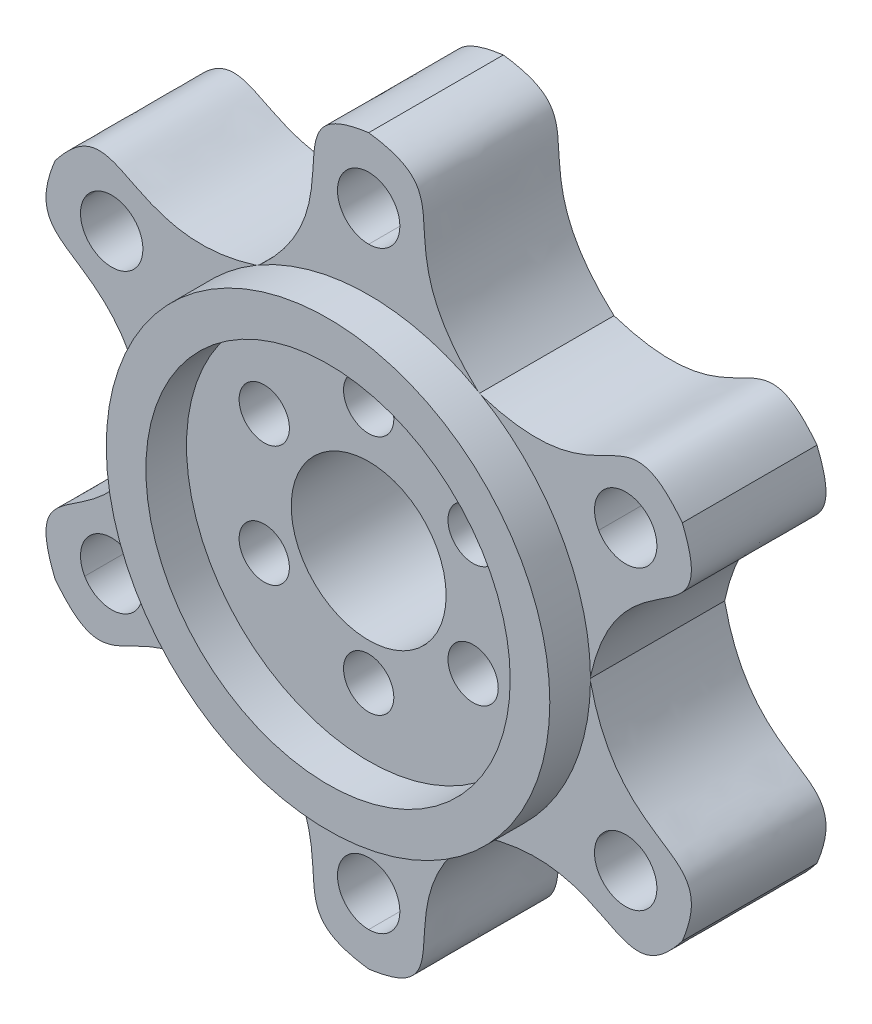
SolidWorks part; units mm, degrees
ref_plane "Front Plane" through (0, 0, 0) normal (0, 0, 1) x (1, 0, 0)
ref_plane "Top Plane" through (0, 0, 0) normal (0, 1, 0) x (1, 0, 0)
ref_plane "Right Plane" through (0, 0, 0) normal (1, 0, 0) x (0, 0, -1)
sketch "Sketch1" plane through (0, 0, 0) normal (0, 0, 1) x (1, 0, 0)
  line L0 (0, -55) -> (0, 55) construction
  line L1 (0, 0) -> (0, 45.72) construction
  circle A0 centre (0, 0) radius 9.779
  circle A1 centre (0, 0) radius 45.72
  circle A2 centre (0, 16.002) radius 3.175
  circle A3 centre (13.1849, 8.3897) radius 3.175
  circle A4 centre (13.1849, -6.8349) radius 3.175
  circle A5 centre (0, -14.4471) radius 3.175
  circle A6 centre (-13.1849, -6.8349) radius 3.175
  circle A7 centre (-13.1849, 8.3897) radius 3.175
  circle A8 centre (0, 37.465) radius 3.937
  circle A10 centre (32.4456, 18.7325) radius 3.937
  circle A11 centre (32.4456, -18.7325) radius 3.937
  circle A12 centre (0, -37.465) radius 3.937
  circle A13 centre (-32.4456, -18.7325) radius 3.937
  circle A14 centre (-32.4456, 18.7325) radius 3.937
  point P21 (0, 0.7774)
  point P36 (0, 0)
  dimension "D1" = 19.558
  dimension "D2" = 91.44
  dimension "D3" = 6.35
  dimension "D6" = 7.874
  dimension "D4" = 16.002
  dimension "D8" = 37.465
  dimension "D5" = 6
  dimension "D7" = 6
extrude "Boss-Extrude3" add sketch "Sketch1" along normal blind 17
sketch "Sketch2" plane through (0, 0, 17) normal (0, 0, 1) x (1, 0, 0)
  line L0 (0, -9.35) -> (0, 9.35) construction
  line L1 (-32.4456, 18.7325) -> (0, 37.465) construction
  line L2 (-16.2228, 28.0988) -> (-4.8895, 8.4689) construction
  line L3 (16.1678, 28.1305) -> (4.8344, 8.5004) construction
  line L6 (32.4456, -18.7325) -> (32.4456, 18.7325) construction
  line L7 (32.4456, 18.7325) -> (0, 37.465) construction
  line L8 (9.35, 0) -> (-9.35, 0) construction
  circle A0 centre (0, 0) radius 27.94 construction
  circle A1 centre (0, 0) radius 45.72 construction
  circle A2 centre (0, 0) radius 9.779 construction
  circle A3 centre (0, 0) radius 45.72
  spline S0 degree 3 poles (-13.97, 24.1967) (-0.9195, 35.9832) (-13.1193, 43.9586) (0, 45.72) knots 0 0 0 0 1 1 1 1
  spline S1 degree 3 poles (13.97, 24.1967) (0.9195, 35.9832) (13.1193, 43.9586) (0, 45.72) knots 0 0 0 0 1 1 1 1
  spline S2 degree 3 poles (-27.94, 0) (-31.6221, 17.1953) (-44.6289, 10.6177) (-39.5947, 22.86) knots 0 0 0 0 1 1 1 1
  spline S3 degree 3 poles (-13.97, 24.1967) (-30.7026, 18.7879) (-31.5096, 33.3409) (-39.5947, 22.86) knots 0 0 0 0 1 1 1 1
  spline S4 degree 3 poles (-13.97, -24.1967) (-30.7026, -18.7879) (-31.5096, -33.3409) (-39.5947, -22.86) knots 0 0 0 0 1 1 1 1
  spline S5 degree 3 poles (-27.94, 0) (-31.6221, -17.1953) (-44.6289, -10.6177) (-39.5947, -22.86) knots 0 0 0 0 1 1 1 1
  spline S6 degree 3 poles (13.97, -24.1967) (30.7026, -18.7879) (31.5096, -33.3409) (39.5947, -22.86) knots 0 0 0 0 1 1 1 1
  spline S7 degree 3 poles (27.94, 0) (31.6221, -17.1953) (44.6289, -10.6177) (39.5947, -22.86) knots 0 0 0 0 1 1 1 1
  spline S8 degree 3 poles (13.97, -24.1967) (0.9195, -35.9832) (13.1193, -43.9586) (0, -45.72) knots 0 0 0 0 1 1 1 1
  spline S9 degree 3 poles (-13.97, -24.1967) (-0.9195, -35.9832) (-13.1193, -43.9586) (0, -45.72) knots 0 0 0 0 1 1 1 1
  spline S10 degree 3 poles (27.94, 0) (31.6221, 17.1953) (44.6289, 10.6177) (39.5947, 22.86) knots 0 0 0 0 1 1 1 1
  spline S11 degree 3 poles (13.97, 24.1967) (30.7026, 18.7879) (31.5096, 33.3409) (39.5947, 22.86) knots 0 0 0 0 1 1 1 1
  point P2 (13.97, 24.1967)
  point P5 (-16.2228, 28.0988)
  point P6 (16.1678, 28.1305)
  point P35 (0, 46.99)
  circle M8 centre (0, 0) radius 45.72
  dimension "D1" = 55.88
  dimension "D2" = 18.796
extrude "Cut-Extrude1" cut sketch "Sketch2" against normal blind 22.86 contours S1 S11 M8 | S5 S2 A3 | S10 S7 A3 | S6 S8 A3 | S9 S4 M8 | S3 S0 M8 region at (38.1245, 0, 17) region at (19.0622, 33.0168, 17) region at (19.0622, -33.0168, 17) region at (-19.0622, 33.0168, 17) region at (-19.0622, -33.0168, 17) region at (-38.1245, 0, 17)
sketch "Sketch4" plane through (0, 0, 17) normal (0, 0, 1) x (1, 0, 0)
  circle A0 centre (0, 0) radius 9.779 construction
  circle A1 centre (0, 0) radius 9.779 construction
  circle A2 centre (0, 0) radius 28
  circle A3 centre (0, 0) radius 23
  dimension "D1" = 56
  dimension "D2" = 46
extrude "Boss-Extrude4" add sketch "Sketch4" along normal blind 5.1308 contours A2 | A3
ref_plane "Plane1" through (0, 0, 0) normal (1, 0, 0) x (0, 0, -1)
ref_plane "Plane2" through (0, 0, 0) normal (-0.5, -0.866, 0) x (-0.866, 0.5, 0)
ref_plane "Plane3" through (0, 0, 0) normal (-0.5, 0.866, 0) x (0.866, 0.5, 0)
split line "Split Line1"
split line "Split Line2"
split line "Split Line3"
ref_axis "Axis1" through (0, 0, 17) along (0, 0, -1)
